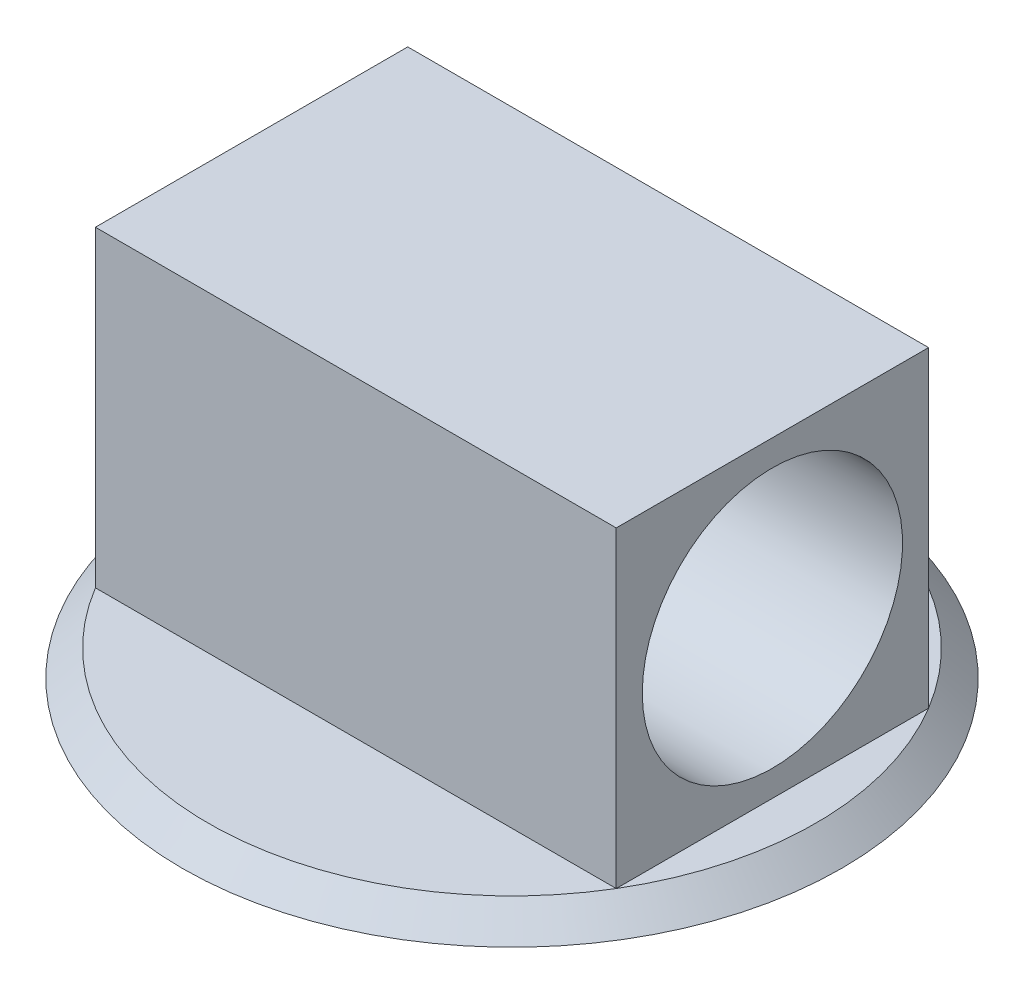
SolidWorks part; units mm, degrees
ref_plane "Front Plane" through (0, 0, 0) normal (0, 0, 1) x (1, 0, 0)
ref_plane "Top Plane" through (0, 0, 0) normal (0, 1, 0) x (1, 0, 0)
ref_plane "Right Plane" through (0, 0, 0) normal (1, 0, 0) x (0, 0, -1)
sketch "Sketch1" plane through (0, 0, 0) normal (0, 1, 0) x (1, 0, 0)
  line L0 (0, 16) -> (0, 0) construction
  line L1 (-8, 16) -> (8, 16)
  line L2 (-8, 16) -> (-8, 0)
  line L10 (8, 16) -> (8, 0)
  line L11 (-8, 0) -> (8, 0)
  dimension "D1" = 16
  dimension "D2" = 16
sketch "Sketch13" plane through (0, 0, 0) normal (0, 1, 0) x (1, 0, 0)
  line L0 (0, 16) -> (0, 0) construction
  circle A0 centre (0, 8) radius 20
  dimension "D1" = 40
extrude "Boss-Extrude2" add sketch "Sketch13" along normal blind 1.5
chamfer "Chamfer1" distance 2.5 angle 45 1 edges at (0, 1.5, 12)
sketch "Esquisse1" plane through (0, 1.5, 0) normal (0, 1, 0) x (1, 0, 0)
  line L1 (-15.0083, -1) -> (15.0083, -1)
  line L2 (-15.0083, -1) -> (-15.0083, 17)
  line L3 (-15.0083, 17) -> (15.0083, 17)
  line L4 (15.0083, -1) -> (15.0083, 17)
  circle A0 centre (0, 8) radius 17.5 construction
  dimension "D1" = 18
  dimension "D2" = 9
  dimension "D3" = 9
extrude "Boss.-Extru.1" add sketch "Esquisse1" along normal blind 18
sketch "Esquisse2" plane through (-15.0083, 0, 0) normal (-1, 0, 0) x (0, 0, 1)
  line L0 (-17, 19.5) -> (-17, 1.5) construction
  line L1 (-17, 19.5) -> (1, 19.5) construction
  circle A0 centre (-8, 10.5) radius 7.5
  dimension "D3" = 15
  dimension "D1" = 9
  dimension "D2" = 9
extrude "Enlèv. mat.-Extru.1" cut sketch "Esquisse2" against normal blind 40
